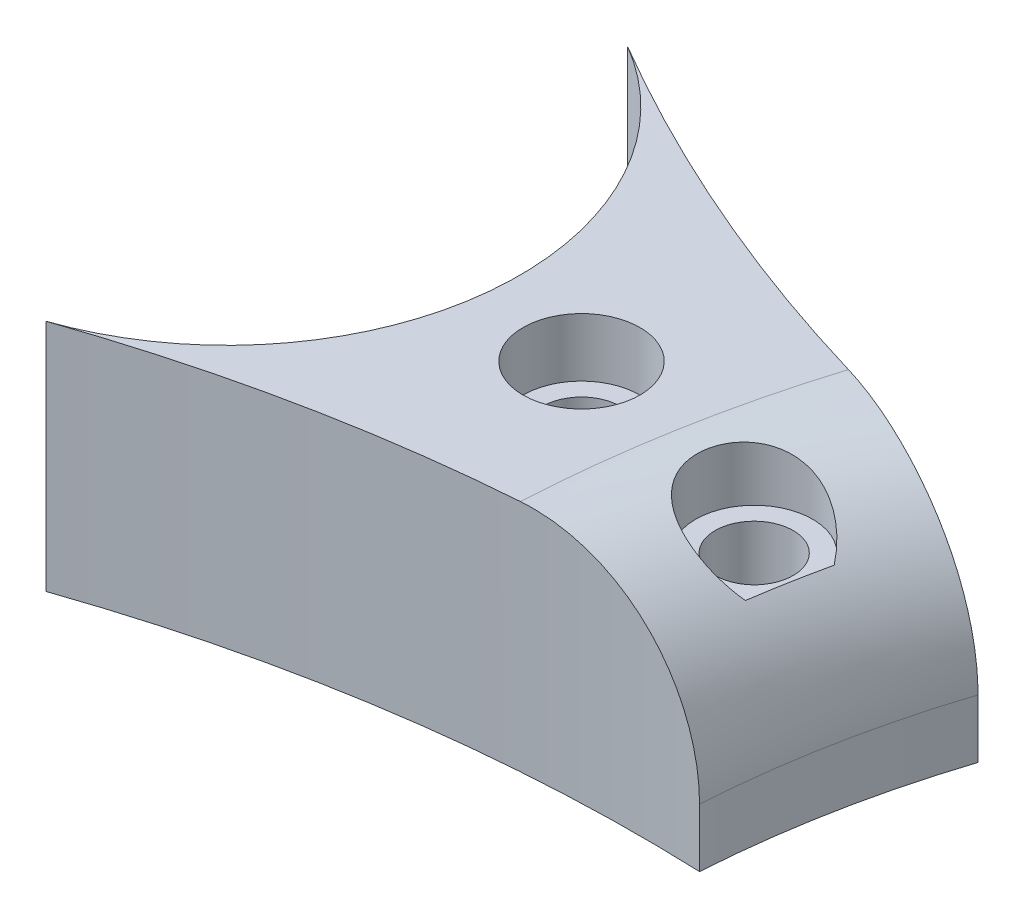
SolidWorks part; units mm, degrees
ref_plane "Front Plane" through (0, 0, 0) normal (0, 0, 1) x (1, 0, 0)
ref_plane "Top Plane" through (0, 0, 0) normal (0, 1, 0) x (1, 0, 0)
ref_plane "Right Plane" through (0, 0, 0) normal (1, 0, 0) x (0, 0, -1)
sketch "Sketch4" plane through (0, 0, 0) normal (0, 1, 0) x (1, 0, 0)
  arc A0 (-15.7434, -13.557) -> (13.452, -9.2409) centre (10.3533, -89.1809) cw
  arc A1 (15.7434, 2.7448) -> (13.452, -9.2409) centre (62.3515, -12.3776) ccw
  circle A2 centre (-0.2367, -1.606) radius 2
  circle A3 centre (9.7042, -2.6919) radius 2
  arc A4 (-13.0407, 13.557) -> (15.7434, 2.7448) centre (32.5341, 91.1646) ccw
  arc A5 (-15.7434, -13.557) -> (-13.0407, 13.557) centre (-20.6365, 0.6224) ccw
extrude "Boss-Extrude3" add sketch "Sketch4" along normal blind 12
sketch "Sketch5" plane through (0, 12, 0) normal (0, 1, 0) x (1, 0, 0)
  circle A0 centre (-0.2367, -1.606) radius 3
  circle A1 centre (9.7042, -2.6919) radius 3
  dimension "D1" = 6
  dimension "D2" = 6
extrude "Cut-Extrude1" cut sketch "Sketch5" against normal blind 3
fillet "Fillet2" radius 9 1 edges at (14.2231, 12, 3.1765)
equation "\"`0.00mm\"=8"
